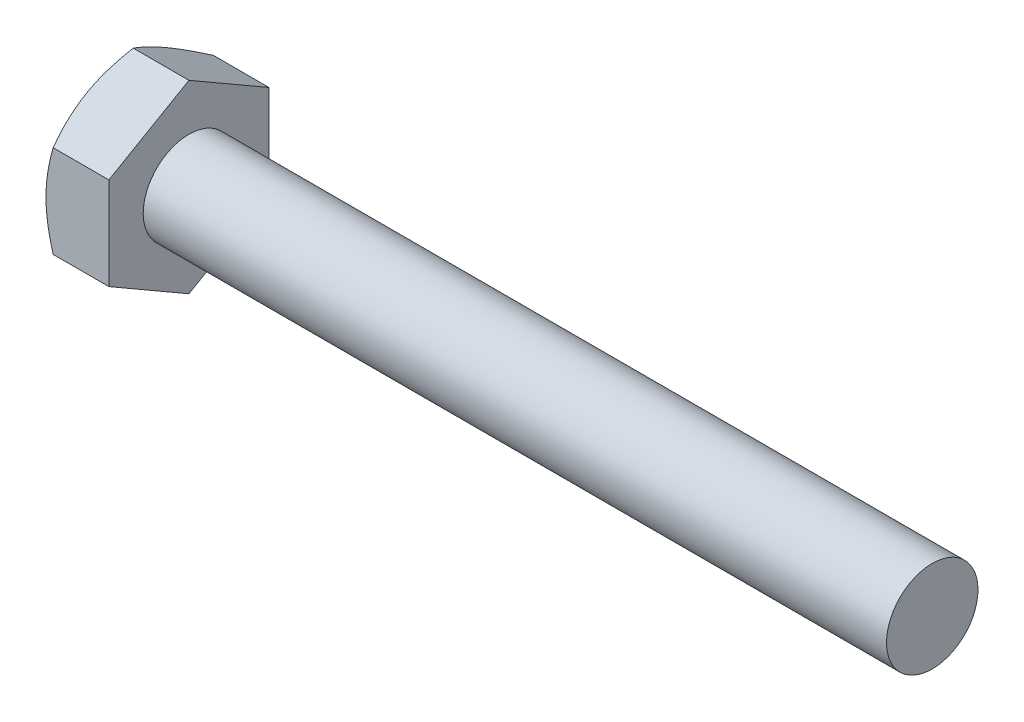
SolidWorks part; units mm, degrees
material "AISI 1020"
ref_plane "Front Plane" through (0, 0, 0) normal (0, 0, 1) x (1, 0, 0)
ref_plane "Top Plane" through (0, 0, 0) normal (0, 1, 0) x (1, 0, 0)
ref_plane "Right Plane" through (0, 0, 0) normal (1, 0, 0) x (0, 0, -1)
sketch "Sketch1" plane through (0, 0, 0) normal (0, 0, 1) x (1, 0, 0)
  line L0 (-27.9797, 0) -> (27.9797, 0) construction
  line L1 (27.9797, 3.175) -> (27.9797, -3.175) construction
  line L2 (-23.6141, 5.5562) -> (-23.6141, -5.5562) construction
  line L3 (-27.9797, 5.5562) -> (-27.9797, -5.5562) construction
  point P9 (-23.6141, 0)
  point P10 (24.8047, -3.175)
  point P11 (16.0734, 0)
  dimension "D1" = 3.175
ref_plane "Plane2" through (27.9797, 0, 0) normal (1, 0, 0) x (0, 0, -1)
sketch "Sketch5" plane through (27.9797, 0, 0) normal (1, 0, 0) x (0, 0, -1)
  circle A0 centre (0, 0) radius 3.175
extrude "Boss-Extrude3" add sketch "Sketch5" against normal up to vertex (51.5938 mm away) up to point (-23.6141, 0, 0)
sketch "Sketch6" plane through (-23.6141, 0, 0) normal (-1, 0, 0) x (0, 0, 1)
  line L0 (0, 5.5562) -> (0, -5.5562) construction
  line L1 (5.5562, 3.2079) -> (0, 6.4158)
  line L2 (0, 6.4158) -> (-5.5563, 3.2079)
  line L3 (-5.5563, 3.2079) -> (-5.5563, -3.2079)
  line L4 (-5.5563, -3.2079) -> (0, -6.4158)
  line L5 (0, -6.4158) -> (5.5563, -3.2079)
  line L6 (5.5563, -3.2079) -> (5.5562, 3.2079)
  circle A0 centre (0, 0) radius 5.5562 construction
extrude "Boss-Extrude4" add sketch "Sketch6" along normal up to vertex (4.3656 mm away) up to point (-27.9797, -5.5562, 0)
sketch "Sketch7" plane through (-27.9797, 0, 0) normal (-1, 0, 0) x (0, 0, 1)
  circle A0 centre (0, 0) radius 5.5562 construction
  circle A1 centre (0, 0) radius 5.5562
sketch "Sketch12" plane through (-27.9797, 0, 0) normal (-1, 0, 0) x (0, 0, 1)
  line L0 (0, 4.2783) -> (0, 2.3892) construction
  line L1 (0.1667, 4.2783) -> (0.1667, 2.3892)
  line L2 (-0.1667, 4.2783) -> (-0.1667, 2.3892)
  line L3 (0, 3.175) -> (0, -3.175) construction
  arc A0 (0.1667, 4.2783) -> (-0.1667, 4.2783) centre (0, 4.2783) ccw
  arc A1 (-0.1667, 2.3892) -> (0.1667, 2.3892) centre (0, 2.3892) ccw
  circle A3 centre (0, 0) radius 2.2225 construction
  circle A4 centre (0, 0) radius 4.445 construction
  point P2 (0, 3.3337)
  dimension "D1" = 4.445
  dimension "D3" = 8.89
  dimension "D2" = 0.3334
sketch "Sketch8" plane through (-27.9797, 0, 0) normal (-1, 0, 0) x (0, 0, 1)
  circle A0 centre (0, 0) radius 5.5562 construction
  circle A1 centre (0, 0) radius 5.5562
extrude "Cut-Extrude3" cut sketch "Sketch8" against normal through all draft 60 flip side to cut
ref_plane "Split Plane" through (16.0734, 0, 0) normal (1, 0, 0) x (0, 0, -1)
ref_axis "Center Axis 1" through (-27.9797, 0, 0) along (1, 0, 0)
ref_plane "Contact Plane 1" through (-23.6141, 0, 0) normal (1, 0, 0) x (0, 0, -1)
split "Split1" [suppressed] bodies to split 113
sketch "Sketch9" [suppressed] plane through (27.9797, 0, 0) normal (1, 0, 0) x (0, 0, -1)
  circle A1 centre (0, 0) radius 3.175
  circle A2 centre (0, 0) radius 3.175
  dimension "D1" = 0
curve "Helix/Spiral1" [suppressed] pitch 0.9071 height 12.8134 turns 14.125 parameters "Pitch"=0.9071
chamfer "Chamfer1" [suppressed] distance 0.6804 angle 45
sketch "Sketch10" [suppressed] plane through (0, 0, 0) normal (0, 0, 1) x (1, 0, 0)
  line L0 (27.9797, 3.175) -> (28.3199, 2.5858)
  line L1 (28.3199, 2.5858) -> (28.4333, 2.5858)
  line L2 (28.4333, 2.5858) -> (28.7734, 3.175)
  line L3 (27.9797, 3.175) -> (28.7734, 3.175)
  line L4 (28.3766, 3.175) -> (28.3766, 2.5858) construction
  line L5 (28.1498, 2.8804) -> (28.6033, 2.8804) construction
  dimension "D1" = 60
  dimension "D2" = 0.1134
  dimension "D3" = 0.4536
sweep "Cut-Sweep1" [suppressed] cut profiles "Sketch10" path "Helix/Spiral1"
sketch "Sketch15" [suppressed] plane through (16.0734, 0, 0) normal (1, 0, 0) x (0, 0, -1)
  circle A0 centre (0, 0) radius 3.175 construction
  circle A1 centre (0, 0) radius 3.175
extrude "Boss-Extrude5" [suppressed] add sketch "Sketch15" along normal through all draft 40
equation "\"D2@Sketch10\" = \"Pitch@Helix/Spiral1\"*.125"
equation "\"D3@Sketch10\" = \"Pitch@Helix/Spiral1\"*.5"
equation "\"D3@Helix/Spiral1\"=\"Min Thread@Sketch1\"+\"Pitch@Helix/Spiral1\""
equation "\"D1@Chamfer1\" = \"Pitch@Helix/Spiral1\"*.75"
equation "\"D1@Sketch12\" = \"Hex@Sketch1\"*.4"
equation "\"D3@Sketch12\" = \"Hex@Sketch1\"*.8"
equation "\"D2@Sketch12\" = \"Hex@Sketch1\"*.03"
equation "\"D1@Sketch1\" = \"Pitch@Helix/Spiral1\"*3.5"
